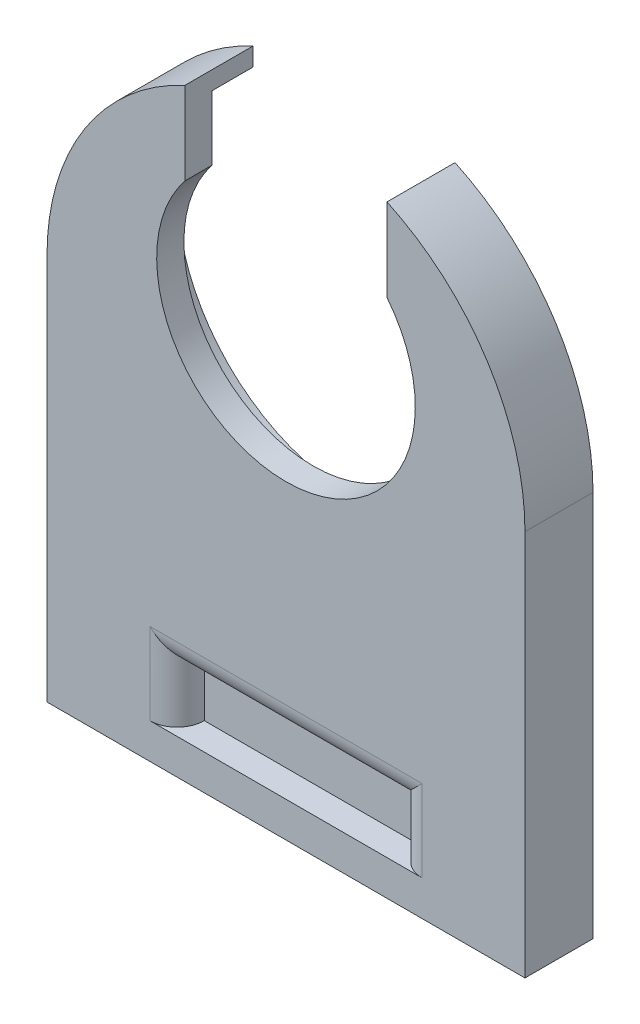
SolidWorks part; units mm, degrees
ref_plane "Front Plane" through (0, 0, 0) normal (0, 0, 1) x (1, 0, 0)
ref_plane "Top Plane" through (0, 0, 0) normal (0, 1, 0) x (1, 0, 0)
ref_plane "Right Plane" through (0, 0, 0) normal (1, 0, 0) x (0, 0, -1)
sketch "Sketch1" plane through (0, 0, 0) normal (0, 0, 1) x (1, 0, 0)
  line L0 (5.32, 14.0026) -> (5.32, 14.6195)
  line L1 (0, 0) -> (17.56, 0)
  line L2 (0, 0) -> (0, 6.55)
  line L3 (0, 6.55) -> (17.56, 6.55)
  line L4 (17.56, 0) -> (17.56, 6.55)
  line L6 (12.24, 14.0026) -> (12.24, 14.6195)
  arc A0 (5.32, 14.6195) -> (0, 6.55) centre (8.78, 6.55) ccw
  arc A1 (5.32, 14.0026) -> (12.24, 14.0026) centre (8.78, 8.5) ccw
  arc A2 (17.56, 6.55) -> (12.24, 14.6195) centre (8.78, 6.55) ccw
  dimension "D4" = 13
  dimension "D1" = 17.56
  dimension "D2" = 6.55
  dimension "D5" = 1.95
  dimension "D6" = 5.32
extrude "Boss-Extrude1" add sketch "Sketch1" along normal blind 1.5 contours A1 L3 L2 L1 L4 | A1 L0 A0 L3 | L3 A2 L6 A1 region at (1.98, 9.9073, 0) region at (8.78, 1.8126, 0) region at (15.58, 9.9073, 0)
sketch "Sketch3" plane through (0, 0, 1.5) normal (0, 0, 1) x (1, 0, 0)
  line L5 (5.32, 14.0026) -> (5.32, 14.6195)
  line L6 (0, 6.55) -> (0, 0)
  line L7 (0, 0) -> (17.56, 0)
  line L8 (17.56, 0) -> (17.56, 6.55)
  line L9 (12.24, 14.6195) -> (12.24, 14.0026)
  line L10 (5.32, 14.0026) -> (5.32, 14.6195)
  line L11 (0, 6.55) -> (0, 0)
  line L12 (0, 0) -> (17.56, 0)
  line L13 (17.56, 0) -> (17.56, 6.55)
  line L14 (12.24, 14.6195) -> (12.24, 14.0026)
  line L15 (0, 0) -> (17.56, 0)
  line L16 (17.56, 6.55) -> (17.56, 0)
  line L17 (0, 0) -> (0, 6.55)
  line L18 (5.32, 14.6195) -> (12.24, 14.6195)
  arc A3 (5.32, 14.0026) -> (12.24, 14.0026) centre (8.78, 8.5) ccw
  arc A4 (5.32, 14.6195) -> (0, 6.55) centre (8.78, 6.55) ccw
  arc A5 (17.56, 6.55) -> (12.24, 14.6195) centre (8.78, 6.55) ccw
  arc A6 (5.32, 14.0026) -> (12.24, 14.0026) centre (8.78, 8.5) ccw
  arc A7 (5.32, 14.6195) -> (0, 6.55) centre (8.78, 6.55) ccw
  arc A8 (17.56, 6.55) -> (12.24, 14.6195) centre (8.78, 6.55) ccw
  arc A9 (17.56, 6.55) -> (12.24, 14.6195) centre (8.78, 6.55) ccw
  arc A10 (0, 6.55) -> (5.32, 14.6195) centre (8.78, 6.55) cw
  arc M9 (12.24, 14.0026) -> (5.32, 14.0026) centre (8.78, 8.5) cw
  line M10 (5.32, 14.0026) -> (5.32, 14.6195)
  arc M11 (5.32, 14.6195) -> (0, 6.55) centre (8.78, 6.55) ccw
  line M12 (0, 6.55) -> (0, 0)
  line M13 (0, 0) -> (17.56, 0)
  line M14 (17.56, 0) -> (17.56, 6.55)
  arc M15 (17.56, 6.55) -> (12.24, 14.6195) centre (8.78, 6.55) ccw
  line M16 (12.24, 14.6195) -> (12.24, 14.0026)
  dimension "D1" = 0
extrude "Boss-Extrude2" add sketch "Sketch3" along normal blind 1 contours M16 M9 M10 M11 M12 M13 M14 M15 | L18 M10 M9 M16 region at (8.78, 1.7715, 1.5) region at (8.78, 8.4788, 1.5)
sketch "Sketch4" plane through (0, 0, 1.5) normal (0, 0, -1) x (-1, 0, 0)
  circle A0 centre (-8.78, 8.5) radius 4.75
  dimension "D1" = 9.5
extrude "Cut-Extrude1" cut sketch "Sketch4" against normal through all
sketch "Sketch5" plane through (0, 0, 0) normal (0, -1, 0) x (1, 0, 0)
  line L1 (0, 2.5) -> (17.56, 2.5)
  line L2 (0, 2.5) -> (0, 0)
  line L3 (0, 0) -> (17.56, 0)
  line L4 (17.56, 2.5) -> (17.56, 0)
extrude "Boss-Extrude3" add sketch "Sketch5" along normal blind 0.15
sketch "Sketch6" plane through (0, -0.15, 0) normal (0, -1, 0) x (1, 0, 0)
  line L4 (0, 2.5) -> (0, 0)
  line L5 (0, 0) -> (17.56, 0)
  line L6 (17.56, 0) -> (17.56, 2.5)
  line L7 (17.56, 2.5) -> (0, 2.5)
  line L8 (0, 2.5) -> (0, 0)
  line L9 (0, 0) -> (17.56, 0)
  line L10 (17.56, 0) -> (17.56, 2.5)
  line L11 (17.56, 2.5) -> (0, 2.5)
  dimension "D1" = 0
extrude "Boss-Extrude4" add sketch "Sketch6" along normal blind 7.5
sketch "Sketch9" plane through (0, 0, 2.5) normal (0, 0, 1) x (1, 0, 0)
  line L0 (12.78, -4.3532) -> (17.56, -4.3532) construction
  line L1 (12.78, -6.3532) -> (4.78, -6.3532)
  line L2 (12.78, -6.3532) -> (12.78, -4.3532)
  line L3 (12.78, -4.3532) -> (4.78, -4.3532)
  line L4 (4.78, -6.3532) -> (4.78, -4.3532)
  line L5 (17.56, -7.65) -> (17.56, 6.55) construction
  line L6 (4.78, -4.3532) -> (0, -4.3532) construction
  line L7 (0, 6.55) -> (0, -7.65) construction
  dimension "D1" = 2
  dimension "D2" = 8
extrude "Cut-Extrude2" cut sketch "Sketch9" against normal blind 1
fillet "Fillet1" radius 1 3 edges at (4.78, -5.3532, 2.5) (12.78, -5.3532, 2.5) (8.78, -4.3532, 2.5)
sketch "Sketch10" plane through (0, 14.6195, 0) normal (0, 1, 0) x (1, 0, 0)
  line L4 (12.24, -1.5) -> (5.32, -1.5)
  line L5 (5.32, -1.5) -> (5.32, -2.5)
  line L6 (5.32, -2.5) -> (12.24, -2.5)
  line L7 (12.24, -2.5) -> (12.24, -1.5)
  line L8 (12.24, -1.5) -> (5.32, -1.5)
  line L9 (5.32, -1.5) -> (5.32, -2.5)
  line L10 (5.32, -2.5) -> (12.24, -2.5)
  line L11 (12.24, -2.5) -> (12.24, -1.5)
  dimension "D1" = 0
extrude "Cut-Extrude3" cut sketch "Sketch10" against normal up to next
ref_plane "Plane1" through (8.78, 0, 0) normal (-1, 0, 0) x (0, 0, 1)
sketch "Sketch11" plane through (5.32, 0, 0) normal (1, 0, 0) x (0, 0, -1)
  line L1 (-2.5, 14.6195) -> (0, 14.6195)
  line L2 (-2.5, 14.6195) -> (-2.5, 11.0306)
  line L3 (-2.5, 11.0306) -> (0, 11.0306)
  line L4 (0, 14.6195) -> (0, 11.0306)
extrude "Cut-Extrude4" cut sketch "Sketch11" against normal blind 0.25
mirror "Mirror1" about plane through (8.78, 0, 0) normal (-1, 0, 0) of "Cut-Extrude4"
